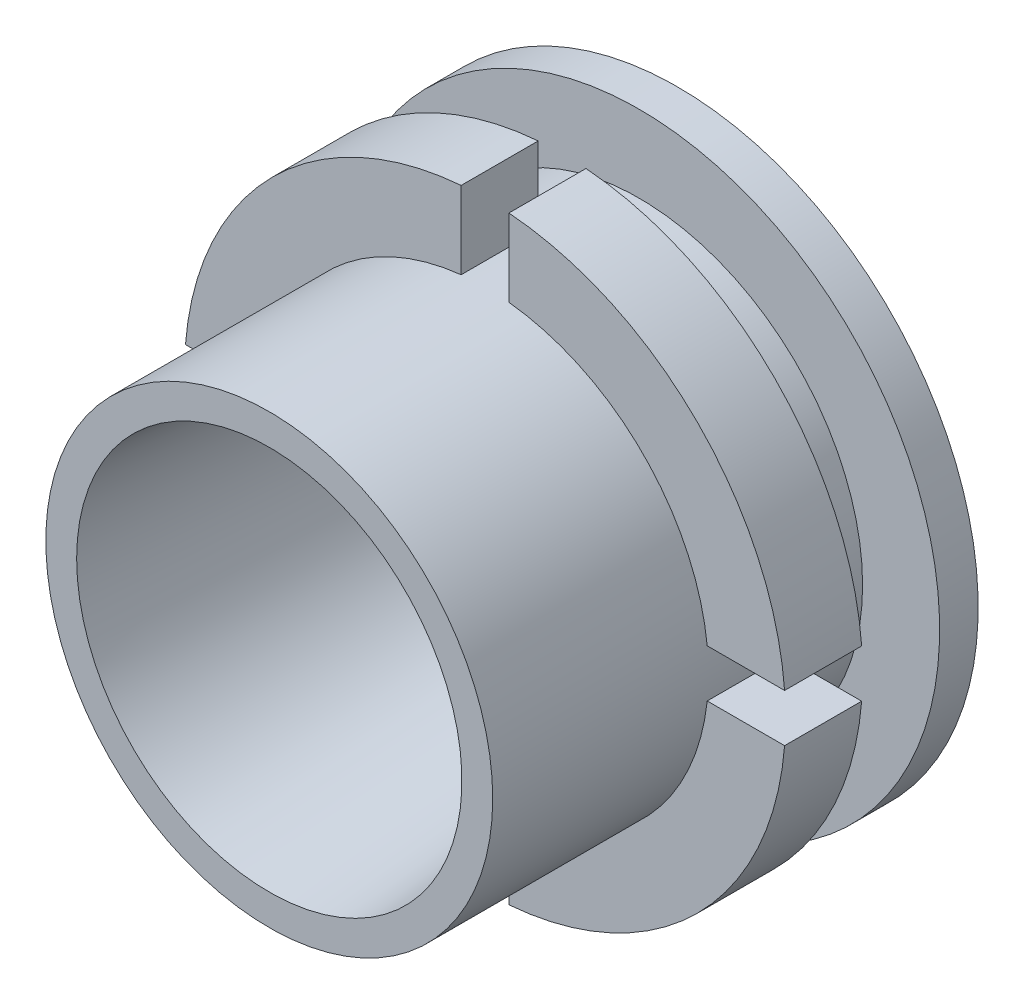
SolidWorks part; units mm, degrees
ref_plane "Спереди" through (0, 0, 0) normal (0, 0, 1) x (1, 0, 0)
ref_plane "Сверху" through (0, 0, 0) normal (0, 1, 0) x (1, 0, 0)
ref_plane "Справа" through (0, 0, 0) normal (1, 0, 0) x (0, 0, -1)
sketch "Sketch1" plane through (0, 0, 0) normal (0, 0, 1) x (1, 0, 0)
  line L0 (0, 48.6842) -> (0, -51.3158) construction
  line L1 (-51.8421, 0) -> (48.1579, 0) construction
  circle A0 centre (0, 0) radius 25
  circle A1 centre (0, 0) radius 29
  dimension "D1" = 50
  dimension "D2" = 4
extrude "Boss-Extrude1" add sketch "Sketch1" against normal blind 53 contours A1
sketch "Sketch2" plane through (0, 0, 0) normal (0, 0, -1) x (-1, 0, 0)
  circle A0 centre (0, 0) radius 25 construction
  circle A1 centre (0, 0) radius 25
extrude "Cut-Extrude1" cut sketch "Sketch2" along normal through all draft 5
sketch "Sketch3" plane through (0, 0, 0) normal (1, 0, 0) x (0, 0, -1)
  line L0 (33.1719, 0) -> (-37.1927, 0) construction
  line L2 (40, 23.5) -> (40, 20.5) construction
  line L3 (41.5, 22) -> (41.5, 20.5)
  line L4 (41.5, 20.5) -> (38.5, 20.5)
  line L5 (38.5, 20.5) -> (38.5, 22)
  arc A0 (41.5, 22) -> (38.5, 22) centre (40, 22) ccw
  dimension "D1" = 3
  dimension "D2" = 40
  dimension "D3" = 20.5
  dimension "D4" = 3
ref_axis "Axis1" through (0, 0, -80.9) along (0, 0, 1)
revolve "Cut-Revolve1" cut sketch "Sketch3" angle 360 about L0
sketch "Эскиз1" plane through (0, 0, -53) normal (0, 0, -1) x (-1, 0, 0)
  circle A0 centre (0, 0) radius 29 construction
  circle A1 centre (0, 0) radius 29
  circle A2 centre (0, 0) radius 39
  dimension "D1" = 10
extrude "Бобышка-Вытянуть1" add sketch "Эскиз1" against normal blind 5
ref_plane "Плоскость1" through (0, 0, -38) normal (0, 0, -1) x (-1, 0, 0)
sketch "Эскиз2" plane through (0, 0, -38) normal (0, 0, -1) x (-1, 0, 0)
  circle A1 centre (0, 0) radius 39
  circle A2 centre (0, 0) radius 39
  circle A3 centre (0, 0) radius 29
  circle A4 centre (0, 0) radius 29
  dimension "D1" = 0
  dimension "D2" = 0
extrude "Бобышка-Вытянуть2" add sketch "Эскиз2" against normal blind 10
ref_plane "Плоскость2" through (0, 45, 0) normal (0, 1, 0) x (1, 0, 0)
sketch "Эскиз3" plane through (0, 45, 0) normal (0, 1, 0) x (1, 0, 0)
  line L0 (-3, 42.4831) -> (3, 42.4831) construction
  line L1 (3.1, 22.3708) -> (3.1, 42.5831)
  line L2 (-3.1, 42.5831) -> (3.1, 42.5831)
  line L3 (-3.1, 42.5831) -> (-3.1, 22.3708)
  line L4 (-3.1, 22.3708) -> (3.1, 22.3708)
  line L17 (-3, 42.4831) -> (-3, 22.4708) construction
  line L18 (-3, 22.4708) -> (3, 22.4708) construction
  line L19 (3, 22.4708) -> (3, 42.4831) construction
  dimension "D2" = 0.1
extrude "Вырез-Вытянуть1" cut sketch "Эскиз3" against normal up to surface (16.1662 mm away) up to face at (29, 0, 0)
pattern_circular "Круговой массив1" count 4 over 360 of "Вырез-Вытянуть1"
equation "\"диаметр трубы мама\"=50"
equation "\"диаметр уплотнителя\"=3"
equation "\"градус конуса\"=5"
